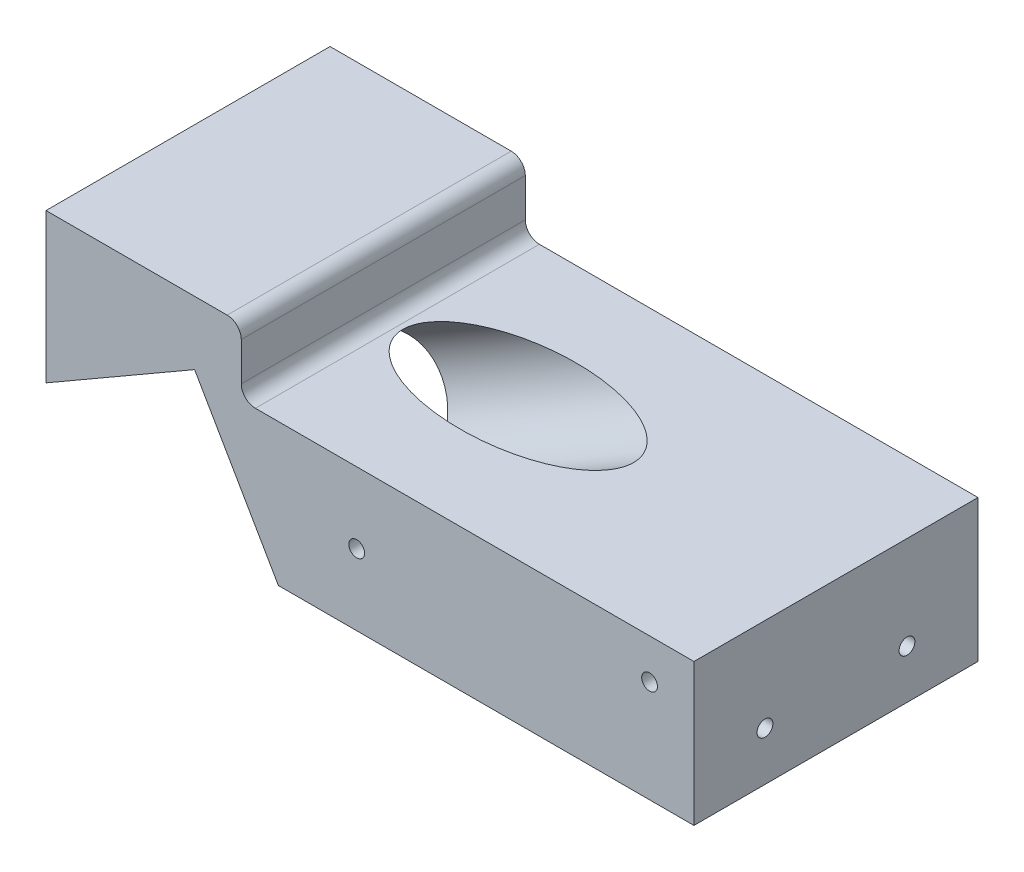
SolidWorks part; units mm, degrees
material "6061-T4 (SS)"
ref_plane "Front Plane" through (0, 0, 0) normal (0, 0, 1) x (1, 0, 0)
ref_plane "Top Plane" through (0, 0, 0) normal (0, 1, 0) x (1, 0, 0)
ref_plane "Right Plane" through (0, 0, 0) normal (1, 0, 0) x (0, 0, -1)
sketch "Sketch1" plane through (0, 0, 0) normal (0, 1, 0) x (1, 0, 0)
  line L1 (-36.5, 16) -> (36.5, 16)
  line L2 (-36.5, 16) -> (-36.5, -16)
  line L3 (-36.5, -16) -> (36.5, -16)
  line L4 (36.5, 16) -> (36.5, -16)
  line L5 (-36.5, 16) -> (36.5, -16) construction
  line L6 (-36.5, -16) -> (36.5, 16) construction
  point P0 (0, 0)
  dimension "D1" = 73
  dimension "D2" = 32
extrude "Boss-Extrude1" add sketch "Sketch1" along normal blind 16
sketch "Sketch78" plane through (0, 0, 16) normal (0, 0, 1) x (1, 0, 0)
  line L0 (-14.5, 16) -> (-12.9125, 16)
  line L1 (-36.5, 16) -> (-14.5, 16)
  line L2 (-36.5, 16) -> (-36.5, 23.5)
  line L3 (-36.5, 23.5) -> (-16.0875, 23.5)
  line L4 (-14.5, 17.5875) -> (-14.5, 21.9125)
  line L5 (-36.5, 16) -> (36.5, 16) construction
  line L6 (-12.9125, 16) -> (-12.9125, 17.5875) construction
  line L7 (-12.9125, 17.5875) -> (-14.5, 17.5875) construction
  arc A0 (-16.0875, 23.5) -> (-14.5, 21.9125) centre (-16.0875, 21.9125) cw
  arc A1 (-12.9125, 16) -> (-14.5, 17.5875) centre (-12.9125, 17.5875) cw
  dimension "D3" = 1.5875
  dimension "D1" = 7.5
  dimension "D2" = 22
  dimension "D4" = 1.5875
  dimension "D5" = 1.5875
extrude "Boss-Extrude4" add sketch "Sketch78" against normal up to surface (32 mm away) up to face at (0, 8, -16)
sketch "Sketch79" plane through (0, 0, -16) normal (0, 0, -1) x (-1, 0, 0)
  line L0 (-32.5, 1.97) -> (23.61, 1.97) construction
  line L1 (-32.5, 1.97) -> (-32.5, 29.2) construction
  line L2 (23.61, 1.97) -> (-20.8992, 27.6674) construction
  line L3 (33.135, 1.97) -> (34.135, 1.97) construction
  line L4 (14.4951, 7.2325) -> (19.7576, 16.3474)
  line L5 (19.7576, 16.3474) -> (36.5, 6.6812)
  line L6 (36.5, 23.5) -> (36.5, 0) construction
  line L7 (14.4951, 7.2325) -> (10.3194, 0)
  line L8 (-36.5, 0) -> (36.5, 0) construction
  line L9 (10.3194, 0) -> (36.5, 0)
  line L10 (36.5, 0) -> (36.5, 6.6812)
  circle A0 centre (23.61, 1.97) radius 9.525 construction
  circle A1 centre (23.61, 1.97) radius 10.525 construction
  dimension "D4" = 19.05
  dimension "D1" = 27.23
  dimension "D2" = 56.11
  dimension "D3" = 30
  dimension "D5" = 1
extrude "Cut-Extrude23" cut sketch "Sketch79" against normal blind 41
sketch "Sketch26" plane through (0, 0, 0) normal (0, -1, 0) x (1, 0, 0)
  line L0 (-10.3194, 16) -> (36.5, 16) construction
  line L1 (36.5, -16) -> (42.85, -16)
  line L2 (36.5, -16) -> (36.5, 16)
  line L3 (36.5, 16) -> (42.85, 16)
  line L4 (42.85, -16) -> (42.85, 16)
  dimension "D1" = 6.35
sketch "Sketch15" plane through (-36.5, 0, 0) normal (-1, 0, 0) x (0, 0, 1)
  line L0 (-10, 14.6812) -> (10, 14.6812) construction
  line L1 (-10, 14.6812) -> (-16, 14.6812) construction
  line L3 (10, 14.6812) -> (16, 14.6812) construction
  line L6 (16, 23.5) -> (16, 6.6812) construction
  line L7 (-16, 23.5) -> (-16, 6.6812) construction
  line L9 (16, 6.6812) -> (-16, 6.6812) construction
  dimension "D3" = 20
  dimension "D4" = 8
sketch "Sketch14" plane through (-13.4261, 5.3809, -20) normal (-0.866, -0.5, 0) x (0, 0, 1)
  line L0 (4, 2.138) -> (20, 2.138) construction
  line L1 (20, 2.138) -> (36, 2.138) construction
  line L2 (36, 12.663) -> (36, -6.2133) construction
  line L3 (4, 12.663) -> (4, -6.2133) construction
  circle A0 centre (20, 2.138) radius 6.5
  dimension "D1" = 13
extrude "Cut-Extrude2" cut sketch "Sketch14" against normal blind 33 and the other way blind 41
hole_wizard "#2-56 Tapped Hole1" positions "Sketch80" profile "Sketch81" tap size "#2-56" standard "ANSI Inch"
sketch "Sketch80" plane through (-36.5, 0, 0) normal (-1, 0, 0) x (0, 0, 1)
  point P0 (-10, 14.6812)
  point P3 (10, 14.6812)
sketch "Sketch81" plane through (-36.5, 14.6812, -10) normal (0, 1, 0) x (0, 0, 1)
  line L0 (0, 0) -> (0, 6.8842)
  line L1 (0, 6.8842) -> (0.889, 6.35)
  line L2 (0.889, 6.35) -> (0.889, 0)
  line L5 (0.889, 0) -> (0, 0)
  line L10 (0, 6.8842) -> (-0.889, 6.35) construction
  line L11 (0, -6.35) -> (0, 107.95) construction
  dimension "Tap Drill Dia." = 1.778
  dimension "Tap Drill Depth" = 6.35
  dimension "Drill Angle" = 118
sketch "Sketch59" plane through (0, 0, -16) normal (0, 0, -1) x (-1, 0, 0)
  line L0 (36.5, 16) -> (36.5, 0) construction
  line L1 (36.5, 0) -> (-36.5, 0) construction
  line L2 (-36.5, 0) -> (-36.5, 16) construction
  line L3 (36.5, 23.5) -> (36.5, 6.6812) construction
  line L4 (-36.5, 16) -> (36.5, 16) construction
  line L5 (-36.5, 8) -> (36.5, 8) construction
  line L7 (-36.5, 16) -> (12.9125, 16) construction
  line L8 (-31.5, 11.5) -> (-31.5, 8) construction
  line L10 (-36.5, 16) -> (-36.5, 0) construction
  point P7 (-36.5, -1.0965)
  point P10 (-31.5, 11.5)
  point P11 (1.5, 8)
  point P14 (-42.85, 0)
  dimension "D1" = 5
  dimension "D2" = 35
  dimension "D3" = 3.5
hole_wizard "#2-56 Tapped Hole2" positions "Sketch82" profile "Sketch83" tap size "#2-56" standard "ANSI Inch"
sketch "Sketch82" plane through (0, 0, -16) normal (0, 0, -1) x (-1, 0, 0)
  point P0 (-31.5, 11.5)
  point P3 (1.5, 8)
sketch "Sketch83" plane through (31.5, 11.5, -16) normal (1, 0, 0) x (0, 1, 0)
  line L0 (0, 0) -> (0, 6.8842)
  line L1 (0, 6.8842) -> (0.889, 6.35)
  line L2 (0.889, 6.35) -> (0.889, 0)
  line L5 (0.889, 0) -> (0, 0)
  line L10 (0, 6.8842) -> (-0.889, 6.35) construction
  line L11 (0, -6.35) -> (0, 107.95) construction
  dimension "Tap Drill Dia." = 1.778
  dimension "Tap Drill Depth" = 6.35
  dimension "Drill Angle" = 118
hole_wizard "#2-56 Tapped Hole3" positions "Sketch84" profile "Sketch85" tap size "#2-56" standard "ANSI Inch"
sketch "Sketch84" plane through (0, 0, 16) normal (0, 0, 1) x (1, 0, 0)
  point P0 (-1.5, 8)
  point P3 (31.5, 11.5)
sketch "Sketch85" plane through (-1.5, 8, 16) normal (1, 0, 0) x (0, -1, 0)
  line L0 (0, 0) -> (0, 6.8842)
  line L1 (0, 6.8842) -> (0.889, 6.35)
  line L2 (0.889, 6.35) -> (0.889, 0)
  line L5 (0.889, 0) -> (0, 0)
  line L10 (0, 6.8842) -> (-0.889, 6.35) construction
  line L11 (0, -6.35) -> (0, 107.95) construction
  dimension "Tap Drill Dia." = 1.778
  dimension "Tap Drill Depth" = 6.35
  dimension "Drill Angle" = 118
hole_wizard "#2-56 Tapped Hole4" positions "Sketch86" profile "Sketch87" tap size "#2-56" standard "ANSI Inch"
sketch "Sketch86" plane through (-7.7395, -4.4684, 0) normal (-0.866, -0.5, 0) x (0, 0, 1)
  line L0 (-10, 13.5111) -> (10, 13.5111) construction
  circle A1 centre (0, 13.5111) radius 6.5
  circle A2 centre (0, 13.5111) radius 6.5 construction
  point P0 (-10, 13.5111)
  point P2 (10, 13.5111)
  point P19 (0, 13.5111)
  dimension "D1" = 10
sketch "Sketch87" plane through (-14.4951, 7.2325, -10) normal (0, 0, 1) x (0.5, -0.866, 0)
  line L0 (0, 0) -> (0, 6.8842)
  line L1 (0, 6.8842) -> (0.889, 6.35)
  line L2 (0.889, 6.35) -> (0.889, 0)
  line L5 (0.889, 0) -> (0, 0)
  line L10 (0, 6.8842) -> (-0.889, 6.35) construction
  line L11 (0, -6.35) -> (0, 107.95) construction
  dimension "Tap Drill Dia." = 1.778
  dimension "Tap Drill Depth" = 6.35
  dimension "Drill Angle" = 118
hole_wizard "#2-56 Tapped Hole5" positions "Sketch89" profile "Sketch90" tap size "#2-56" standard "ANSI Inch"
sketch "Sketch89" plane through (0, 0, -16) normal (0, 0, -1) x (-1, 0, 0)
  line L0 (36.5, 19) -> (31.5, 19) construction
  line L1 (36.5, 23.5) -> (36.5, 6.6812) construction
  line L2 (31.5, 19) -> (31.5, 23.5) construction
  line L3 (36.5, 23.5) -> (16.0875, 23.5) construction
  point P0 (31.5, 19)
  dimension "D1" = 4.5
  dimension "D2" = 5
sketch "Sketch90" plane through (-31.5, 19, -16) normal (1, 0, 0) x (0, 1, 0)
  line L0 (0, 0) -> (0, 5.2942)
  line L1 (0, 5.2942) -> (0.889, 4.76)
  line L2 (0.889, 4.76) -> (0.889, 0)
  line L5 (0.889, 0) -> (0, 0)
  line L10 (0, 5.2942) -> (-0.889, 4.76) construction
  line L11 (0, -6.35) -> (0, 107.95) construction
  dimension "Tap Drill Dia." = 1.778
  dimension "Tap Drill Depth" = 4.76
  dimension "Drill Angle" = 118
hole_wizard "#2-56 Tapped Hole7" positions "Sketch103" profile "Sketch104" tap size "#2-56" standard "ANSI Inch"
sketch "Sketch103" plane through (36.5, 0, 0) normal (1, 0, 0) x (0, 0, -1)
  line L0 (-16, 5.5) -> (-8, 5.5) construction
  line L1 (-16, 16) -> (-16, 0) construction
  line L2 (-8, 5.5) -> (8, 5.5) construction
  line L3 (8, 5.5) -> (16, 5.5) construction
  line L4 (16, 16) -> (16, 0) construction
  line L5 (16, 5.5) -> (16, 8) construction
  point P0 (-8, 5.5)
  point P3 (8, 5.5)
  dimension "D1" = 2.5
  dimension "D2" = 8
sketch "Sketch104" plane through (36.5, 5.5, 8) normal (0, 1, 0) x (0, 0, -1)
  line L0 (0, 0) -> (0, 13.5342)
  line L1 (0, 13.5342) -> (0.889, 13)
  line L2 (0.889, 13) -> (0.889, 0)
  line L5 (0.889, 0) -> (0, 0)
  line L10 (0, 13.5342) -> (-0.889, 13) construction
  line L11 (0, -6.35) -> (0, 107.95) construction
  dimension "Tap Drill Dia." = 1.778
  dimension "Tap Drill Depth" = 13
  dimension "Drill Angle" = 118
